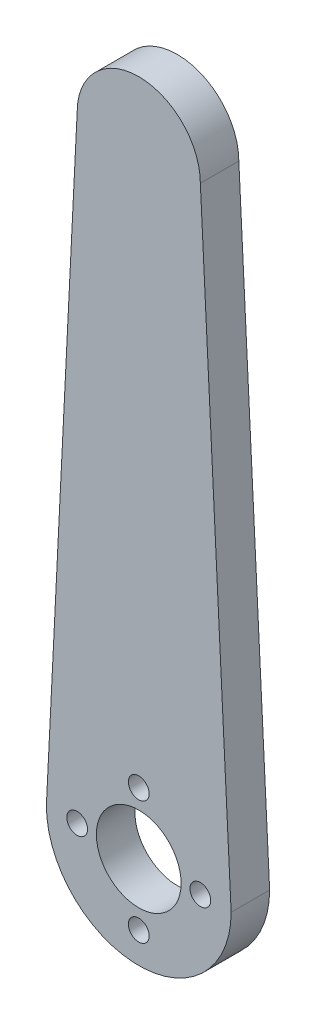
SolidWorks part; units mm, degrees
ref_plane "Front" through (0, 0, 0) normal (0, 0, 1) x (1, 0, 0)
ref_plane "Top" through (0, 0, 0) normal (0, 1, 0) x (1, 0, 0)
ref_plane "Right" through (0, 0, 0) normal (1, 0, 0) x (0, 0, -1)
sketch "Esquisse1" plane through (0, 0, 0) normal (0, 0, 1) x (1, 0, 0)
  line L0 (0, 0) -> (0, 80) construction
  line L1 (12, 0) -> (8, 80)
  line L2 (0, 58) -> (0, 80) construction
  line L3 (0, -12) -> (0, 0) construction
  line L4 (12, 0) -> (-12, 0) construction
  line L5 (8, 80) -> (-8, 80) construction
  line L6 (-12, 0) -> (-8, 80)
  arc A0 (8, 80) -> (-8, 80) centre (0, 80) ccw
  arc A1 (12, 0) -> (-12, 0) centre (0, 0) cw
  dimension "D2" = 12
  dimension "D3" = 8
  dimension "D1" = 80
extrude "Boss.-Extru.1" add sketch "Esquisse1" along normal blind 5
sketch "Esquisse2" plane through (0, 0, 5) normal (0, 0, 1) x (1, 0, 0)
  line L0 (0, 0) -> (8, 0) construction
  circle A0 centre (0, 0) radius 5.5
  circle A1 centre (8, 0) radius 1.35
  circle A2 centre (0, -8) radius 1.35
  circle A3 centre (-8, 0) radius 1.35
  circle A4 centre (0, 8) radius 1.35
  point P5 (-0.5525, 10.0135)
  point P6 (0, 0)
  point P14 (0, 0)
  dimension "D1" = 11
  dimension "D2" = 2.7
  dimension "D3" = 8
  dimension "D4" = 4
extrude "Enlèv. mat.-Extru.1" cut sketch "Esquisse2" against normal through all both and the other way through all
